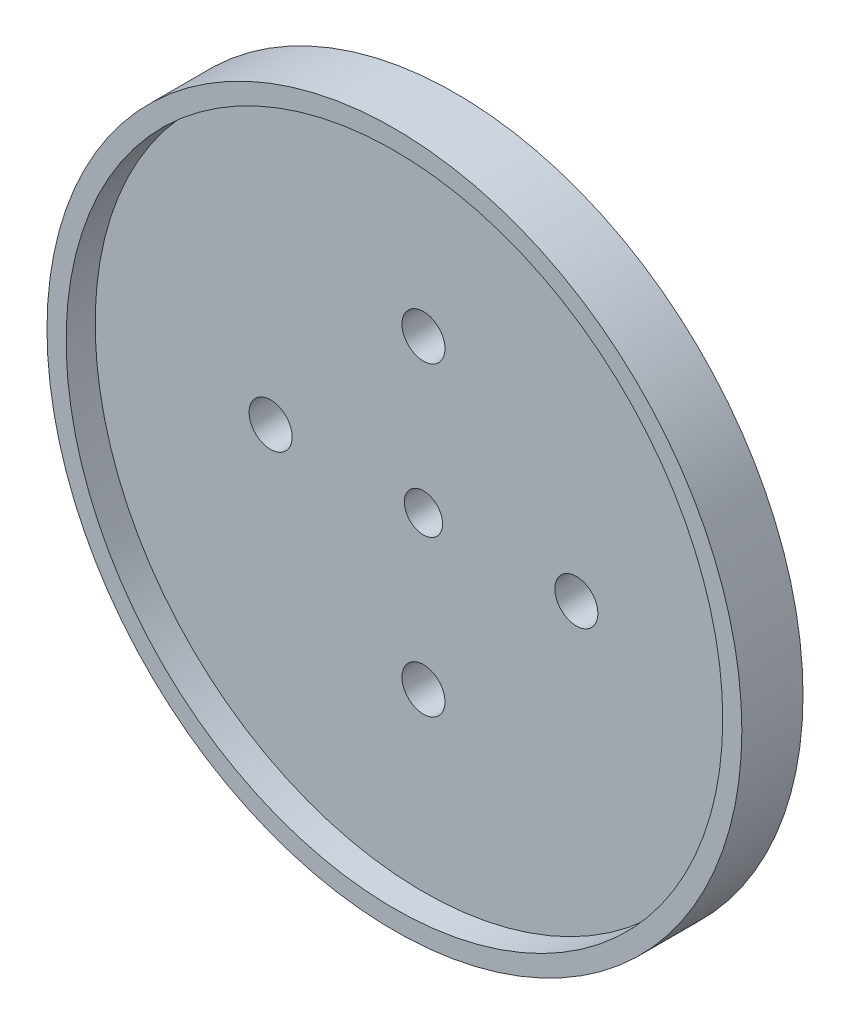
SolidWorks part; units mm, degrees
ref_plane "Front Plane" through (0, 0, 0) normal (0, 0, 1) x (1, 0, 0)
ref_plane "Top Plane" through (0, 0, 0) normal (0, 1, 0) x (1, 0, 0)
ref_plane "Right Plane" through (0, 0, 0) normal (1, 0, 0) x (0, 0, -1)
sketch "Sketch1" plane through (0, 0, 0) normal (0, 0, 1) x (1, 0, 0)
  circle A0 centre (0, 0) radius 57.7215
  dimension "D1" = 115.443
extrude "Extrude1" add sketch "Sketch1" along normal blind 10.16
sketch "Sketch2" plane through (0, 0, 10.16) normal (0, 0, 1) x (1, 0, 0)
  circle A0 centre (0, 0) radius 54.5465
  circle A1 centre (0, 0) radius 57.7215 construction
  dimension "D1" = 3.175
extrude "Extrude2" cut sketch "Sketch2" against normal blind 4.826
hole_wizard "1/4 (0.25) Diameter Hole1" positions "Sketch4" profile "Sketch3" hole size "1/4" standard "Ansi Inch"
sketch "Sketch4" plane through (0, 0, 5.334) normal (0, 0, 1) x (1, 0, 0)
  point P1 (0, 0)
sketch "Sketch3" plane through (0, 0, 5.334) normal (1, 0, 0) x (0, -1, 0)
  line L0 (0, 0) -> (0, 8.2577)
  line L1 (0, 8.2577) -> (3.175, 6.35)
  line L2 (3.175, 6.35) -> (3.175, 0)
  line L5 (3.175, 0) -> (0, 0)
  line L10 (0, 8.2577) -> (-3.175, 6.35) construction
  line L11 (0, -6.35) -> (0, 107.95) construction
  dimension "Hole Dia." = 6.35
  dimension "Hole Depth" = 6.35
  dimension "Drill Angle" = 118
sketch "Sketch5" plane through (0, 0, 5.334) normal (0, 0, 1) x (1, 0, 0)
  line L0 (0, 0) -> (25.4, 0) construction
  dimension "D1" = 25.4
hole_wizard "1/4 Clearance Hole1" positions "3DSketch1" profile "Sketch6" hole size "1/4" standard "Ansi Inch" end condition through all
sketch3d "3DSketch1"
  point P0 (25.4, 0, 5.334)
sketch "Sketch6" plane through (25.4, 0, 5.334) normal (1, 0, 0) x (0, -1, 0)
  line L0 (0, 0) -> (0, 5.334)
  line L1 (0, 5.334) -> (3.5712, 5.334)
  line L2 (3.5712, 5.334) -> (3.5712, 0)
  line L5 (3.5712, 0) -> (0, 0)
  line L11 (0, -6.35) -> (0, 107.95) construction
  dimension "Thru Hole Dia." = 7.1425
  dimension "Thru Hole Depth" = 5.334
pattern_circular "CirPattern1" count 4 over 360 about axis through (0, 0, 10.16) along (0, 0, -1) of "1/4 Clearance Hole1"
